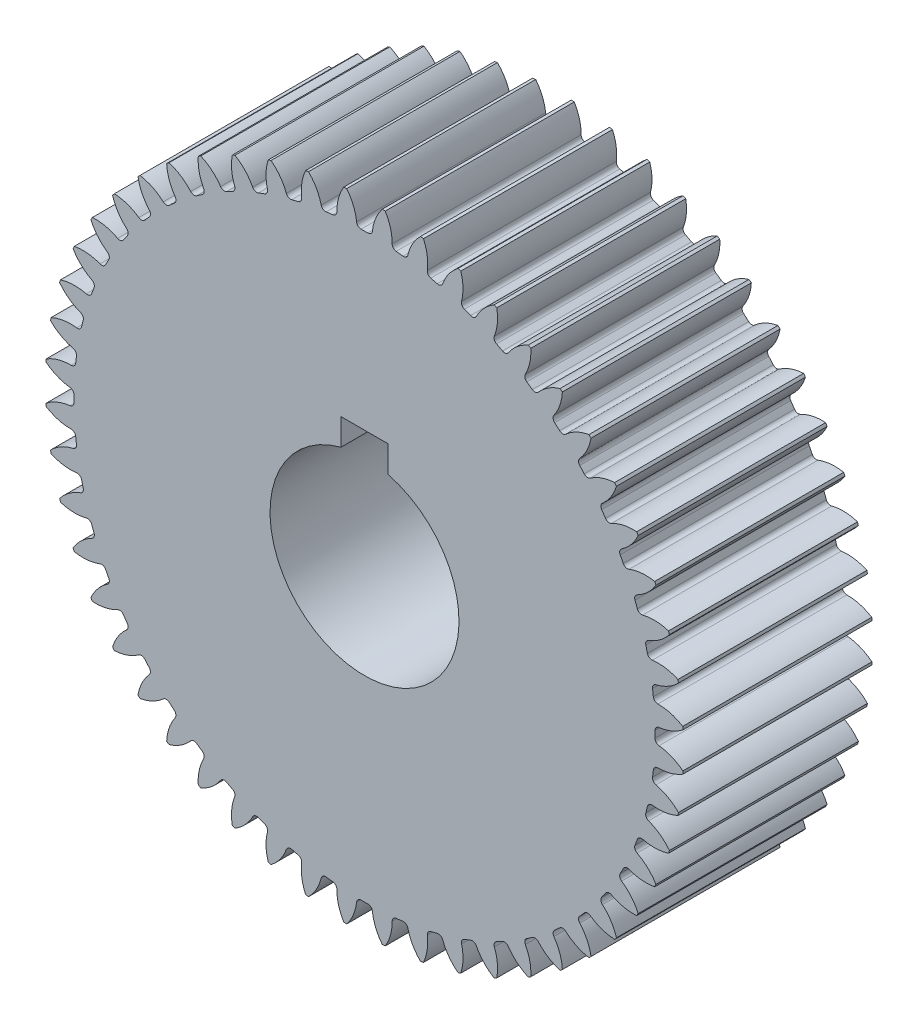
SolidWorks part; units mm, degrees
ref_plane "Front Plane" through (0, 0, 0) normal (1, 0, 0) x (0, 1, 0)
ref_plane "Top Plane" through (0, 0, 0) normal (0, 0, 1) x (0, 1, 0)
ref_plane "Right Plane" through (0, 0, 0) normal (0, 1, 0) x (-1, 0, 0)
sketch "Sketch1" plane through (0, 0, 0) normal (0, 0, 1) x (0, 1, 0)
  circle A0 centre (0, 0) radius 10
  circle A1 centre (0, 0) radius 33.75
  dimension "D1" = 20
  dimension "D2" = 67.5
extrude "Boss-Extrude2" add sketch "Sketch1" along normal blind 20 contours A0 | A1
sketch "Sketch2" plane through (0, 0, 20) normal (0, 0, 1) x (1, 0, 0)
  line L0 (0, 0) -> (0, 33.75) construction
  line L1 (-0.805, 30.7395) -> (0, 0) construction
  line L2 (0, 29.2773) -> (-2.1388, 35.1537) construction
  circle A0 centre (0, 0) radius 33.75 construction
  arc A1 (-0.805, 30.7395) -> (-1.8816, 33.6975) centre (-5.7636, 30.6096) ccw
  arc A2 (1.8816, 33.6975) -> (-1.8816, 33.6975) centre (0, 0) ccw
  arc A3 (1.169, 32.479) -> (-1.169, 32.479) centre (0, 0) ccw
  arc A4 (0.805, 30.7395) -> (-0.805, 30.7395) centre (0, 0) ccw
  arc A5 (0.805, 30.7395) -> (1.8816, 33.6975) centre (5.7636, 30.6096) cw
  point P14 (-1.1024, 32.3062)
  dimension "D1" = 67.5
  dimension "D2" = 65
  dimension "D3" = 3
  dimension "D4" = 20
  dimension "D5" = 2.3385
extrude "Cut-Extrude1" cut sketch "Sketch2" against normal through all contours A2 A1 A4 A5
fillet "Fillet1" radius 0.475 2 edges at (-0.805, 30.7395, 10) (0.805, 30.7395, 10)
pattern_circular "CirPattern1" count 52 over 360 about axis through (0, 0, 20) along (0, 0, 1) of "Fillet1", "Cut-Extrude1"
sketch "Sketch3" plane through (0, 0, 20) normal (0, 0, 1) x (1, 0, 0)
  line L2 (-2.5, 12.5) -> (2.5, 12.5)
  line L3 (-2.5, 12.5) -> (-2.5, 9.6825)
  line L5 (2.5, 12.5) -> (2.5, 9.6825)
  line L6 (-2.5, 12.5) -> (0, 10) construction
  line L7 (0, 10) -> (2.5, 12.5) construction
  circle A0 centre (0, 0) radius 10 construction
  arc A1 (2.5, 9.6825) -> (-2.5, 9.6825) centre (0, 0) ccw
  dimension "D1" = 5
extrude "Cut-Extrude2" cut sketch "Sketch3" against normal through all
sketch "Sketch5" plane through (0, 0, 0) normal (0, 0, -1) x (1, 0, 0)
  line L0 (-2.0378, 33.6884) -> (-1.9622, 32.4395) construction
  line L1 (2.0378, 33.6884) -> (1.9622, 32.4395) construction
  line L2 (-1.6851, 33.7486) -> (-1.1685, 32.4777) construction
  line L3 (-0.6518, 31.2069) -> (-1.6851, 33.7486)
  line L4 (0, 30.75) -> (0, 33.7492) construction
  circle A0 centre (0, 0) radius 30.75 construction
  arc A1 (-1.8816, 33.6975) -> (-2.1939, 33.6786) centre (0, 0) ccw construction
  arc A2 (2.1939, 33.6786) -> (1.8816, 33.6975) centre (0, 0) ccw construction
  arc A3 (-0.8349, 31.1693) -> (-1.8816, 33.6975) centre (-5.7636, 30.6096) ccw construction
  circle A4 centre (0, 0) radius 32.4987 construction
  arc A5 (-0.6518, 31.2069) -> (0, 31.1247) centre (0, 33.7492) ccw
  point P22 (-1.1685, 32.4777)
  dimension "D1" = 1.6851
  dimension "D2" = 2.6246
  dimension "D3" = 2.7437
equation "\"No of teeth\"= 52"
equation "\"Module\"= 1.25"
equation "\"Bore Diameter\"=20"
equation "\"Pressure Angle\"= 20"
equation "\"Outer Diameter\"= ( \"No of teeth\" + 2 ) * \"Module\""
equation "\"Pitch Diameter\"= \"No of teeth\" * \"Module\""
equation "\"Backlash\"= 0.3 * \"Module\""
equation "\"Arc Length\"= ( ( \"Module\" * pi ) / 2 ) + \"Backlash\""
equation "\"Fillet Radius\"= 0.38 * \"Module\""
equation "\"Tooth Depth\"= IIF ( \"Module\" <= 1.25 , \"Module\" * 2.4 , \"Module\" * 2.25 )"
equation "\"D1@Sketch1\"=\"Bore Diameter\""
equation "\"D2@Sketch1\"=\"Outer Diameter\""
equation "\"D1@Sketch2\"=\"Outer Diameter\""
equation "\"D2@Sketch2\"=\"Pitch Diameter\""
equation "\"D3@Sketch2\"=\"Tooth Depth\""
equation "\"D4@Sketch2\"=\"Pressure Angle\""
equation "\"D5@Sketch2\"=\"Arc Length\""
equation "\"D1@Fillet1\"=\"Fillet Radius\""
equation "\"D1@CirPattern1\"=\"No of teeth\""
